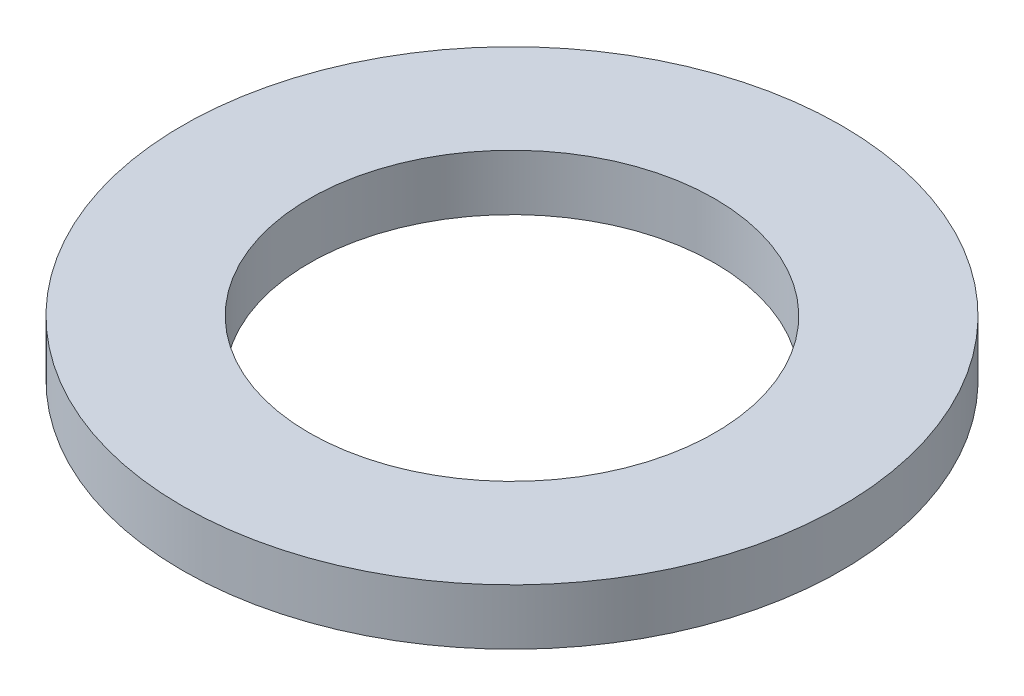
SolidWorks part; units mm, degrees
ref_plane "Front Plane" through (0, 0, 0) normal (0, 0, 1) x (1, 0, 0)
ref_plane "Top Plane" through (0, 0, 0) normal (0, 1, 0) x (1, 0, 0)
ref_plane "Right Plane" through (0, 0, 0) normal (1, 0, 0) x (0, 0, -1)
sketch "Sketch1" plane through (0, 0, 0) normal (0, 1, 0) x (1, 0, 0)
  circle A0 centre (0, 0) radius 65
  dimension "FLANGE_OD" = 130
extrude "Boss-Extrude1" add sketch "Sketch1" along normal blind 11
sketch "Sketch2" plane through (0, 0, 0) normal (0, 1, 0) x (1, 0, 0)
  circle A0 centre (0, 0) radius 40
  dimension "BORE_D" = 80
extrude "Cut-Extrude1" cut sketch "Sketch2" along normal through all
sketch "Sketch3" plane through (0, 11, 0) normal (0, 1, 0) x (1, 0, 0)
  circle A0 centre (0, 0) radius 25.1618 construction
  circle A1 centre (-25.1618, 0) radius 3.7684
  dimension "BOLT_D" = 7.5369
  dimension "BOLT_PCD" = 50.3236
extrude "Cut-Extrude2" cut sketch "Sketch3" against normal blind 10.5322 rebuild error yes
pattern_circular "CirPattern1" count 6 over 360 rebuild error yes
